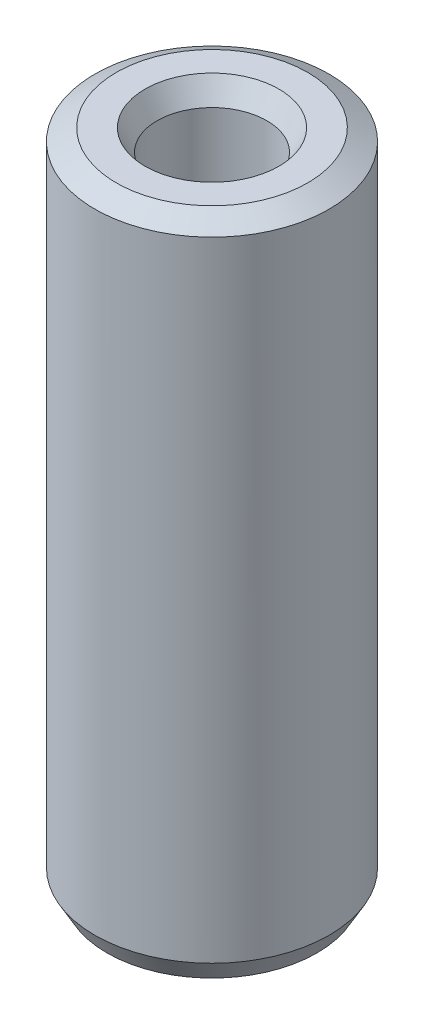
SolidWorks part; units mm, degrees
ref_plane "Front Plane" through (0, 0, 0) normal (0, 0, 1) x (1, 0, 0)
ref_plane "Top Plane" through (0, 0, 0) normal (0, 1, 0) x (1, 0, 0)
ref_plane "Right Plane" through (0, 0, 0) normal (1, 0, 0) x (0, 0, -1)
sketch "Sketch1" plane through (0, 0, 0) normal (0, 1, 0) x (1, 0, 0)
  circle A0 centre (0, 0) radius 37.5
  dimension "SLEEVE_OD" = 75
extrude "Boss-Extrude1" add sketch "Sketch1" along normal blind 212.099
sketch "Sketch2" plane through (0, 0, 0) normal (0, 1, 0) x (1, 0, 0)
  circle A0 centre (0, 0) radius 17.5665
  dimension "BORE_D" = 35.133
extrude "Cut-Extrude1" cut sketch "Sketch2" along normal through all
chamfer "Chamfer1" distance 3.8681 angle 60.516 4 edges at (0, 212.099, 17.5665) (0, 0, 17.5665) (0, 0, 37.5) (0, 212.099, 37.5) first distance on face at (0, 212.099, 17.5665) first distance on face at (0, 0, 17.5665) first distance on face at (0, 212.099, 37.5)
